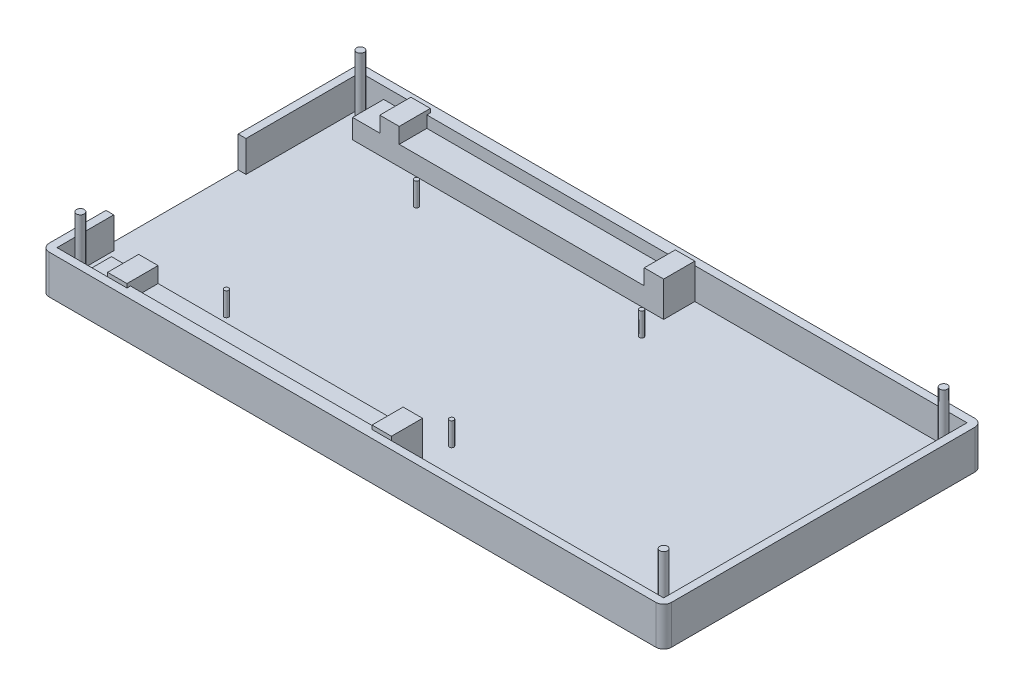
SolidWorks part; units mm, degrees
ref_plane "Front Plane" through (0, 0, 0) normal (0, 0, 1) x (1, 0, 0)
ref_plane "Top Plane" through (0, 0, 0) normal (0, 1, 0) x (1, 0, 0)
ref_plane "Right Plane" through (0, 0, 0) normal (1, 0, 0) x (0, 0, -1)
sketch "Sketch1" plane through (0, 0, 0) normal (0, 1, 0) x (1, 0, 0)
  line L1 (-80, -41) -> (80, -41)
  line L2 (-80, -41) -> (-80, 41)
  line L3 (-80, 41) -> (80, 41)
  line L4 (80, -41) -> (80, 41)
  line L5 (-80, -41) -> (80, 41) construction
  line L6 (-80, 41) -> (80, -41) construction
  point P0 (0, 0)
  dimension "D1" = 160
  dimension "D2" = 82
extrude "Boss-Extrude1" add sketch "Sketch1" along normal blind 10 contours L1 L4 L3 L2
shell "Shell1" thickness 2 removed face at (0, 10, 0)
sketch "Sketch2" plane through (0, 2, 0) normal (0, 1, 0) x (1, 0, 0)
  line L0 (-78, 39) -> (78, 39) construction
  line L1 (-78, -39) -> (-78, 39) construction
  line L2 (0, 39) -> (0, -41) construction
  line L3 (-78, 39) -> (78, 39) construction
  line L4 (-80, -41) -> (80, -41) construction
  line L5 (-80, 0) -> (80, 0) construction
  line L6 (-80, -41) -> (-80, 41) construction
  line L7 (80, -41) -> (80, 41) construction
  circle A0 centre (-75, 36) radius 1
  circle A1 centre (75, 36) radius 1
  circle A2 centre (75, -36) radius 1
  circle A3 centre (-75, -36) radius 1
  dimension "D1" = 3
  dimension "D2" = 3
  dimension "D3" = 2
extrude "Boss-Extrude2" add sketch "Sketch2" along normal blind 16 contours A0 | A3 | A2 | A1
fillet "Fillet1" radius 2 1 edges at (-80, 5, 41)
fillet "Fillet2" radius 2 1 edges at (-80, 5, -41)
fillet "Fillet3" radius 2 1 edges at (80, 5, -41)
fillet "Fillet4" radius 2 1 edges at (80, 5, 41)
sketch "Sketch7" plane through (0, 2, 0) normal (0, 1, 0) x (1, 0, 0)
  line L0 (-49, 24.45) -> (-49, -24.43)
  line L1 (-78, 39) -> (78, 39) construction
  line L2 (-20.05, 24.45) -> (-20.05, -24.43) construction
  line L3 (-49, 0.01) -> (-52.9634, 0.01) construction
  line L4 (-49, 24.45) -> (8.9, 24.45)
  line L5 (8.9, 24.45) -> (8.9, -24.43)
  line L6 (8.9, -24.43) -> (-49, -24.43)
  line L7 (-78, -39) -> (-78, 39) construction
  circle A0 centre (-49, 24.45) radius 0.575
  circle A1 centre (-49, -24.43) radius 0.575
  circle A2 centre (8.9, -24.43) radius 0.575
  circle A3 centre (8.9, 24.45) radius 0.575
  dimension "D3" = 1.15
  dimension "D1" = 48.88
  dimension "D2" = 14.55
  dimension "D4" = 57.9
  dimension "D5" = 29
extrude "Boss-Extrude3" add sketch "Sketch7" along normal blind 6 contours A2 | A1 | A3 | A0
sketch "Sketch10" plane through (-80, 0, 0) normal (-1, 0, 0) x (0, 0, 1)
  line L0 (24.4, 0) -> (-9.6, 0)
  line L2 (39, 0) -> (-39, 0) construction
  line L3 (-9.6, 0) -> (-9.6, 2)
  line L4 (-9.6, 2) -> (24.4, 2)
  line L5 (-9.6, 2) -> (24.4, 2)
  line L6 (-9.6, 2) -> (-9.6, 10.0297)
  line L7 (24.4, 2) -> (24.4, 10.0297)
  line L8 (-9.6, 10.0297) -> (24.4, 10.0297)
  dimension "D1" = 34
  dimension "D2" = 14.6
  dimension "D3" = 2
extrude "Cut-Extrude1" cut sketch "Sketch10" against normal blind 6 contours L4 L7 L8 L6
sketch "Sketch16" plane through (0, 2, 0) normal (0, 1, 0) x (1, 0, 0)
  line L0 (-49, 24.45) -> (-49, 28.15)
  line L1 (-49, -24.43) -> (-49, -28.13)
  line L2 (8.9, -24.43) -> (8.9, -28.13)
  line L3 (8.9, 24.45) -> (8.9, 28.15)
  line L4 (-78, 39) -> (78, 39) construction
  line L5 (-72, 39) -> (8, 39)
  line L6 (-72, 39) -> (-72, 31)
  line L7 (-72, 31) -> (8, 31)
  line L8 (8, 39) -> (8, 31)
  line L9 (78, 0) -> (-83.4739, 0) construction
  line L10 (78, -39) -> (78, 39) construction
  line L11 (8, -39) -> (8, -31)
  line L12 (-72, -39) -> (8, -39)
  line L13 (-72, -39) -> (-72, -31)
  line L14 (-72, -31) -> (8, -31)
  dimension "D1" = 3.7
  dimension "D2" = 3.7
  dimension "D3" = 8
  dimension "D4" = 80
  dimension "D5" = 6
extrude "Boss-Extrude5" add sketch "Sketch16" along normal blind 5 contours L8 L7 L6 L5 | L14 L11 L12 L13
sketch "Sketch18" plane through (0, 7, 0) normal (0, 1, 0) x (1, 0, 0)
  line L0 (-60, 31) -> (3, 31)
  line L1 (-72, 31) -> (8, 31) construction
  line L2 (-60, 39) -> (-60, 31)
  line L3 (-72, 39) -> (8, 39) construction
  line L4 (-60, 39) -> (-65, 39)
  line L5 (-65, 39) -> (-65, 31)
  line L6 (-72, 31) -> (8, 31) construction
  line L7 (-65, 31) -> (-60, 31)
  line L8 (-28.5, 31) -> (-28.5, 39) construction
  line L9 (8, 31) -> (3, 31)
  line L10 (3, 39) -> (3, 31)
  line L11 (8, 39) -> (8, 31)
  line L12 (3, 39) -> (8, 39)
  line L13 (78, 0) -> (-85.0376, 0) construction
  line L14 (78, -39) -> (78, 39) construction
  line L15 (3, -39) -> (8, -39)
  line L16 (8, -39) -> (8, -31)
  line L17 (8, -31) -> (3, -31)
  line L18 (3, -39) -> (3, -31)
  line L19 (-65, -31) -> (-60, -31)
  line L20 (-65, -39) -> (-65, -31)
  line L21 (-60, -39) -> (-65, -39)
  line L22 (-60, -39) -> (-60, -31)
  dimension "D1" = 63
  dimension "D2" = 5
extrude "Boss-Extrude6" add sketch "Sketch18" along normal blind 4 contours L9 L11 L12 L10 | L7 L5 L4 L2 | L16 L17 L18 L15 | L22 L19 L20 L21
sketch "Sketch21" plane through (0, 0, -39) normal (0, 0, 1) x (1, 0, 0)
  line L1 (-60, 10) -> (3, 10)
  line L2 (-60, 10) -> (-60, 7)
  line L3 (-60, 7) -> (3, 7)
  line L4 (3, 10) -> (3, 7)
extrude "Boss-Extrude7" add sketch "Sketch21" along normal blind 0.9
sketch "Sketch22" plane through (0, 0, 39) normal (0, 0, -1) x (-1, 0, 0)
  line L1 (-3, 10) -> (60, 10)
  line L2 (-3, 10) -> (-3, 7)
  line L3 (-3, 7) -> (60, 7)
  line L4 (60, 10) -> (60, 7)
extrude "Boss-Extrude8" add sketch "Sketch22" along normal blind 0.9
